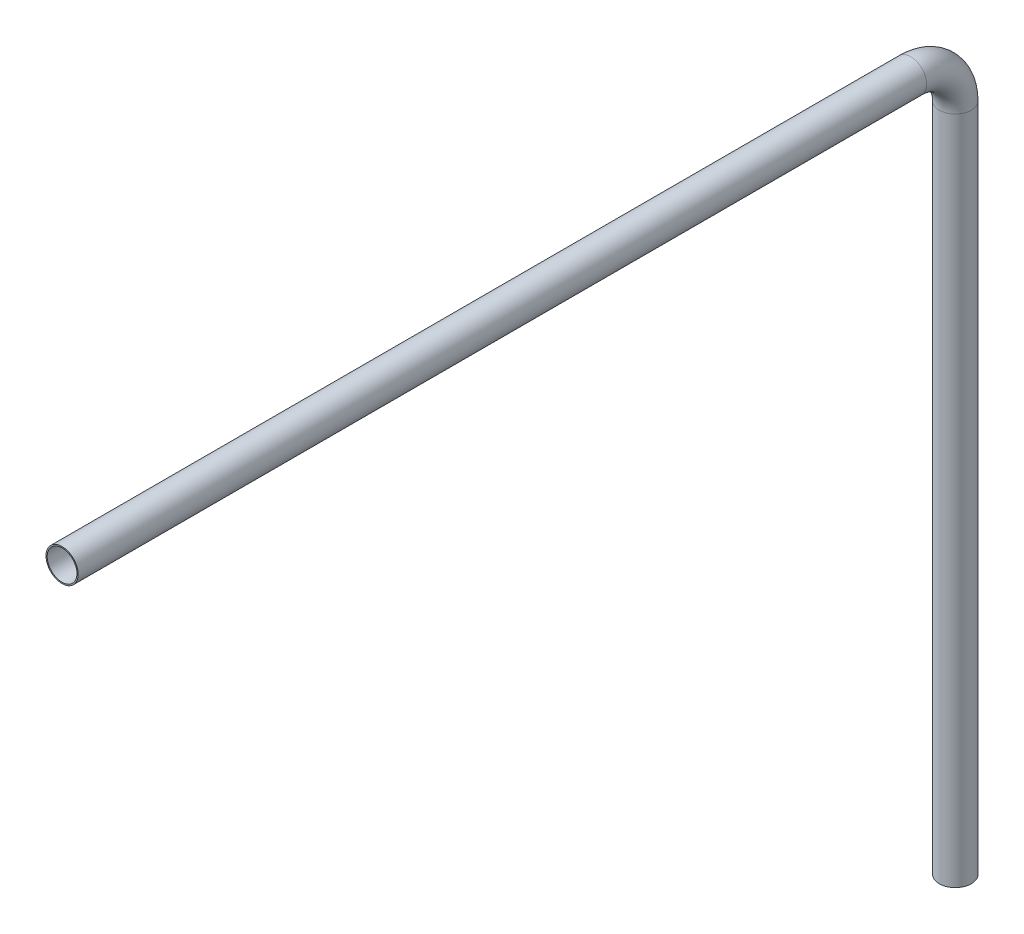
SolidWorks part; units mm, degrees
ref_plane "Front Plane" through (0, 0, 0) normal (0, 0, 1) x (1, 0, 0)
ref_plane "Top Plane" through (0, 0, 0) normal (0, 1, 0) x (1, 0, 0)
ref_plane "Right Plane" through (0, 0, 0) normal (1, 0, 0) x (0, 0, -1)
sketch "Sketch1" plane through (0, 0, 0) normal (1, 0, 0) x (0, 0, -1)
  line L0 (0, 0) -> (0, 1850)
  line L1 (-150, 2000) -> (-3000, 2000)
  arc A0 (0, 1850) -> (-150, 2000) centre (-150, 1850) ccw
  point P6 (0, 2000)
  dimension "D3" = 150
  dimension "D1" = 2000
  dimension "D2" = 3000
sketch "Sketch2" plane through (0, 0, 0) normal (0, 1, 0) x (1, 0, 0)
  circle A0 centre (0, 0) radius 54
  circle A1 centre (0, 0) radius 50
  dimension "D1" = 108
  dimension "D2" = 100
sweep "Sweep1" add profiles "Sketch2" path "Sketch1"
sketch "Sketch3" plane through (0, 0, 0) normal (0, -1, 0) x (1, 0, 0)
  circle A0 centre (0, 0) radius 50 construction
  circle A1 centre (0, 0) radius 54
  circle A2 centre (0, 0) radius 54
  circle A3 centre (0, 0) radius 50
  dimension "D1" = 0
extrude "Boss-Extrude1" add sketch "Sketch3" along normal blind 400
